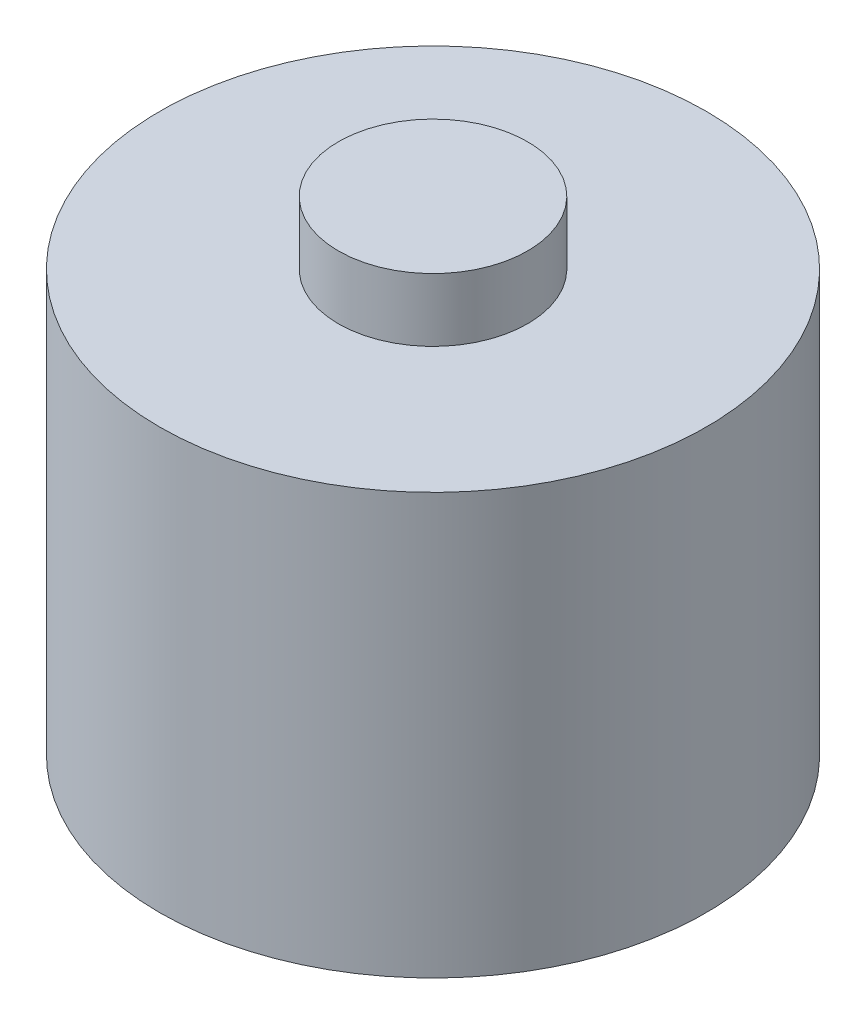
SolidWorks part; units mm, degrees
ref_plane "Front Plane" through (0, 0, 0) normal (0, 0, 1) x (1, 0, 0)
ref_plane "Top Plane" through (0, 0, 0) normal (0, 1, 0) x (1, 0, 0)
ref_plane "Right Plane" through (0, 0, 0) normal (1, 0, 0) x (0, 0, -1)
sketch "Sketch1" plane through (0, 0, 0) normal (0, 1, 0) x (1, 0, 0)
  circle A0 centre (0, 0) radius 13
  dimension "D2" = 26
extrude "Boss-Extrude1" add sketch "Sketch1" along normal blind 20 contours A0
sketch "Sketch3" plane through (0, 20, 0) normal (0, 1, 0) x (1, 0, 0)
extrude "Boss-Extrude2" add sketch "Sketch1<3>" along normal blind 20
sketch "Sketch1<3>" plane through (0, 0, 0) normal (0, 1, 0) x (1, 0, 0) same geometry as "Sketch1"
sketch "Sketch4" plane through (0, 0, 0) normal (0, -1, 0) x (1, 0, 0)
extrude "Boss-Extrude3" add sketch "Sketch1<4>" along normal blind 20
sketch "Sketch1<4>" plane through (0, 0, 0) normal (0, 1, 0) x (1, 0, 0) same geometry as "Sketch1"
sketch "Sketch5" plane through (0, 20, 0) normal (0, 1, 0) x (1, 0, 0)
  circle A0 centre (0, 0) radius 4.5
  dimension "D1" = 9
extrude "Boss-Extrude4" add sketch "Sketch5" along normal blind 3
